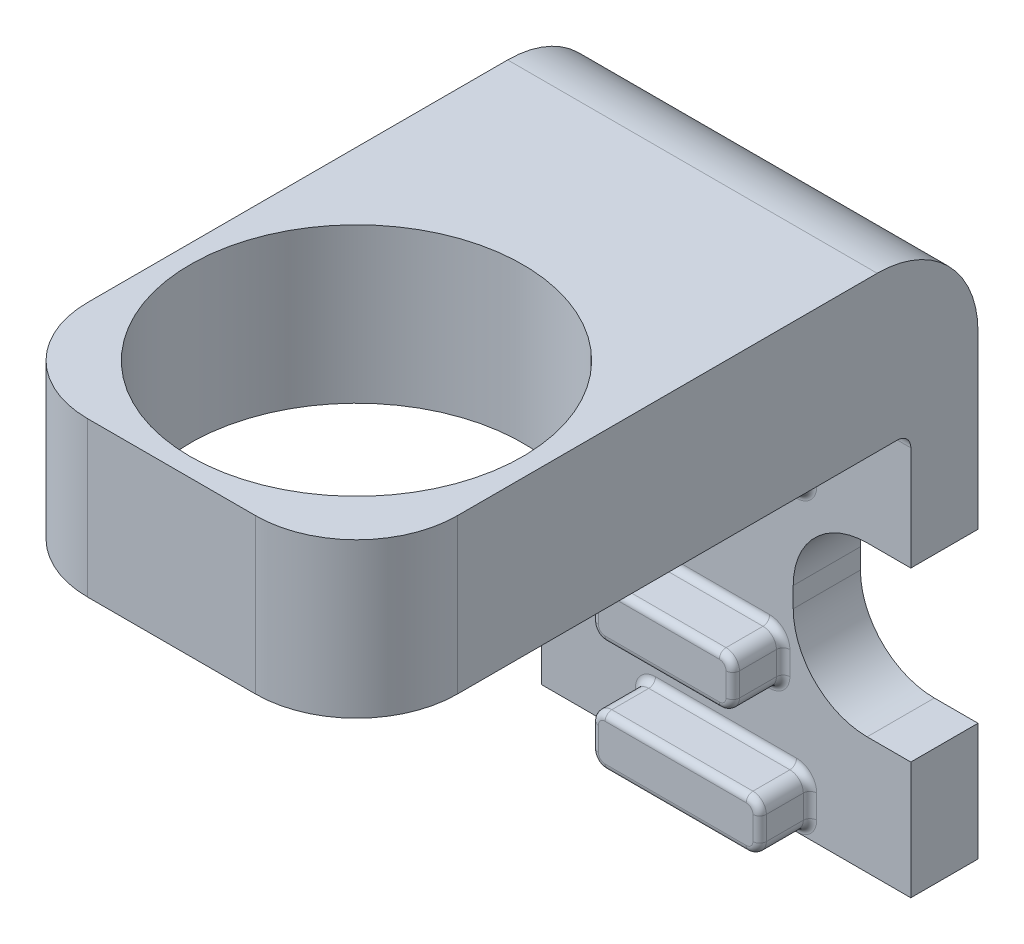
SolidWorks part; units mm, degrees
material "Custom Plastic"
ref_plane "Front Plane" through (0, 0, 0) normal (0, 0, 1) x (1, 0, 0)
ref_plane "Top Plane" through (0, 0, 0) normal (0, 1, 0) x (1, 0, 0)
ref_plane "Right Plane" through (0, 0, 0) normal (1, 0, 0) x (0, 0, -1)
sketch "Sketch1" plane through (0, 0, 0) normal (0, 1, 0) x (1, 0, 0)
  line L1 (-5.5, -5.5) -> (5.5, -5.5)
  line L2 (-5.5, -5.5) -> (-5.5, 5.5)
  line L3 (-5.5, 5.5) -> (5.5, 5.5)
  line L4 (5.5, -5.5) -> (5.5, 5.5)
  line L5 (-5.5, -5.5) -> (5.5, 5.5) construction
  line L6 (-5.5, 5.5) -> (5.5, -5.5) construction
  line L7 (-5.5, 5.5) -> (5.5, 5.5)
  line L8 (-5.5, 5.5) -> (-5.5, 13)
  line L9 (-5.5, 13) -> (5.5, 13)
  line L10 (5.5, 5.5) -> (5.5, 13)
  circle A0 centre (0, 0) radius 4.95
  point P0 (0, 0)
  dimension "D3" = 9.9
  dimension "D1" = 11
  dimension "D2" = 11
  dimension "D4" = 7.5
extrude "Boss-Extrude1" add sketch "Sketch1" along normal blind 4.6 contours L1 L4 L3 L2 A0 | L3 L10 L9 L8 region at (-5.3444, 0, 0) region at (0, 0, -9.25)
sketch "Sketch2" plane through (0, 0, 0) normal (0, -1, 0) x (1, 0, 0)
  line L0 (5.5, -11) -> (-5.5, -11)
  line L4 (5.5, 5.5) -> (-5.5, 5.5)
  line L5 (-5.5, 5.5) -> (-5.5, -13)
  line L6 (-5.5, -13) -> (5.5, -13)
  line L7 (5.5, -13) -> (5.5, 5.5)
  line L8 (5.5, 5.5) -> (-5.5, 5.5)
  line L9 (-5.5, 5.5) -> (-5.5, -13)
  line L10 (-5.5, -13) -> (5.5, -13)
  line L11 (5.5, -13) -> (5.5, 5.5)
  line M8 (-5.5, 5.5) -> (-5.5, -13)
  line M9 (-5.5, -13) -> (5.5, -13)
  line M10 (5.5, -13) -> (5.5, 5.5)
  dimension "D2" = 2
  dimension "D1" = 0
extrude "Boss-Extrude2" add sketch "Sketch2" along normal blind 12 contours L0 M10 M8 M9 region at (0, 0, -12)
sketch "Sketch3" plane through (0, 0, -13) normal (0, 0, -1) x (-1, 0, 0)
  line L0 (-5.5, -6) -> (5.5, -6) construction
  line L1 (-5.5, -8.5) -> (-4.2, -8.5)
  line L2 (-2, -6.3) -> (-2, -5.7)
  line L3 (-4.2, -3.5) -> (-5.5, -3.5)
  line L4 (-5.5, 4.6) -> (-5.5, -12)
  line L5 (-5.5, -12) -> (5.5, -12)
  line L6 (5.5, -12) -> (5.5, 4.6)
  line L7 (5.5, 4.6) -> (-5.5, 4.6)
  line L8 (-5.5, 4.6) -> (-5.5, -12)
  line L9 (-5.5, -12) -> (5.5, -12)
  line L10 (5.5, -12) -> (5.5, 4.6)
  line L11 (5.5, 4.6) -> (-5.5, 4.6)
  arc A1 (-2, -5.7) -> (-4.2, -3.5) centre (-4.2, -5.7) ccw
  arc A2 (-4.2, -8.5) -> (-2, -6.3) centre (-4.2, -6.3) ccw
  line M10 (-5.5, 4.6) -> (-5.5, -12)
  dimension "D5" = 2.2
  dimension "D2" = 3.5
  dimension "D3" = 2.5
  dimension "D4" = 2.5
  dimension "D6" = 6
  dimension "D1" = 0
extrude "Cut-Extrude1" cut sketch "Sketch3" against normal up to surface (2 mm away) contours L0 L2 A1 L3 M10 | L0 L8 L1 A2 L2 region at (3.9195, -4.8522, -13) region at (3.9195, -7.1478, -13) up to face at (0, -6, -11)
fillet "Fillet1" radius 0.4 1 edges at (0, 0, -11)
fillet "Fillet2" radius 3 1 edges at (0, 4.6, -13)
fillet "Fillet3" radius 3 2 edges at (-5.5, 2.3, 5.5) (5.5, 2.3, 5.5)
sketch "Sketch4" plane through (0, 0, -11) normal (0, 0, 1) x (1, 0, 0)
  line L0 (-5.5, 0) -> (5.5, 0) construction
  line L1 (-2.1, -1.7) -> (2.1, -1.7)
  line L2 (-2.5, -2.1) -> (-2.5, -2.8)
  line L3 (-2.1, -3.2) -> (2.1, -3.2)
  line L4 (2.5, -2.1) -> (2.5, -2.8)
  line L5 (-5.5, -12) -> (-5.5, -0.4) construction
  line L10 (5.5, -12) -> (-5.5, -12) construction
  line L12 (-2.1, -11.8) -> (2.1, -11.8)
  line L13 (-2.5, -11.4) -> (-2.5, -10.7)
  line L14 (-2.1, -10.3) -> (2.1, -10.3)
  line L15 (2.5, -11.4) -> (2.5, -10.7)
  line L16 (-2.1, -8.5) -> (1.3, -8.5)
  line L17 (-2.5, -8.1) -> (-2.5, -7.4)
  line L18 (-2.1, -7) -> (1.3, -7)
  line L19 (1.7, -8.1) -> (1.7, -7.4)
  arc A1 (2.1, -10.3) -> (2.5, -10.7) centre (2.1, -10.7) cw
  arc A2 (2.1, -11.8) -> (2.5, -11.4) centre (2.1, -11.4) ccw
  arc A3 (-2.1, -11.8) -> (-2.5, -11.4) centre (-2.1, -11.4) cw
  arc A4 (-2.5, -10.7) -> (-2.1, -10.3) centre (-2.1, -10.7) cw
  arc A5 (-2.1, -8.5) -> (-2.5, -8.1) centre (-2.1, -8.1) cw
  arc A6 (-2.5, -7.4) -> (-2.1, -7) centre (-2.1, -7.4) cw
  arc A7 (1.3, -7) -> (1.7, -7.4) centre (1.3, -7.4) cw
  arc A8 (1.3, -8.5) -> (1.7, -8.1) centre (1.3, -8.1) ccw
  arc A9 (-2.5, -2.8) -> (-2.1, -3.2) centre (-2.1, -2.8) ccw
  arc A10 (2.1, -3.2) -> (2.5, -2.8) centre (2.1, -2.8) ccw
  arc A11 (2.1, -1.7) -> (2.5, -2.1) centre (2.1, -2.1) cw
  arc A12 (-2.1, -1.7) -> (-2.5, -2.1) centre (-2.1, -2.1) ccw
  point P22 (2.5, -11.8)
  point P25 (-2.5, -11.8)
  point P28 (-2.5, -10.3)
  point P31 (-2.5, -8.5)
  point P34 (-2.5, -7)
  point P41 (-2.5, -3.2)
  point P44 (2.5, -3.2)
  point P49 (-2.5, -1.7)
  dimension "D13" = 0.4
  dimension "D1" = 1.7
  dimension "D2" = 5
  dimension "D3" = 3
  dimension "D4" = 1.5
  dimension "D6" = 3
  dimension "D5" = 1.5
  dimension "D7" = 5
  dimension "D8" = 1.5
  dimension "D9" = 1.8
  dimension "D10" = 3
  dimension "D11" = 4.2
  dimension "D12" = 0.2
extrude "Boss-Extrude3" add sketch "Sketch4" along normal up to surface (1.5 mm away)
fillet "Fillet4" radius 0.2 48 edges at (2.5, -2.45, -9.5) (2.3828, -1.8172, -9.5) (0, -1.7, -9.5) (-2.3828, -1.8172, -9.5) (-2.5, -2.45, -9.5) (-2.3828, -3.0828, -9.5) (0, -3.2, -9.5) (1.7, -7.75, -9.5) (1.5828, -7.1172, -9.5) (-0.4, -7, -9.5) (-2.3828, -7.1172, -9.5) (-2.5, -7.75, -9.5) (-2.3828, -8.3828, -9.5) (-0.4, -8.5, -9.5) (-2.3828, -10.4172, -9.5) (-2.5, -11.05, -9.5) (-2.3828, -11.6828, -9.5) (0, -11.8, -9.5) (2.3828, -11.6828, -9.5) (2.5, -11.05, -9.5) (2.3828, -10.4172, -9.5) (2.5, -11.05, -11) (2.3828, -11.6828, -11) (0, -11.8, -11) (-2.3828, -11.6828, -11) (-2.5, -11.05, -11) (-2.3828, -10.4172, -11) (0, -10.3, -11) (1.5828, -8.3828, -11) (-0.4, -8.5, -11) (-2.3828, -8.3828, -11) (-2.5, -7.75, -11) (-2.3828, -7.1172, -11) (-0.4, -7, -11) (1.5828, -7.1172, -11) (2.3828, -1.8172, -11) (2.5, -2.45, -11) (2.3828, -3.0828, -11) (0, -3.2, -11) (-2.3828, -3.0828, -11) (-2.5, -2.45, -11) (-2.3828, -1.8172, -11) (2.3828, -3.0828, -9.5) (1.5828, -8.3828, -9.5) (0, -10.3, -9.5) (2.3828, -10.4172, -11) (1.7, -7.75, -11) (0, -1.7, -11)
